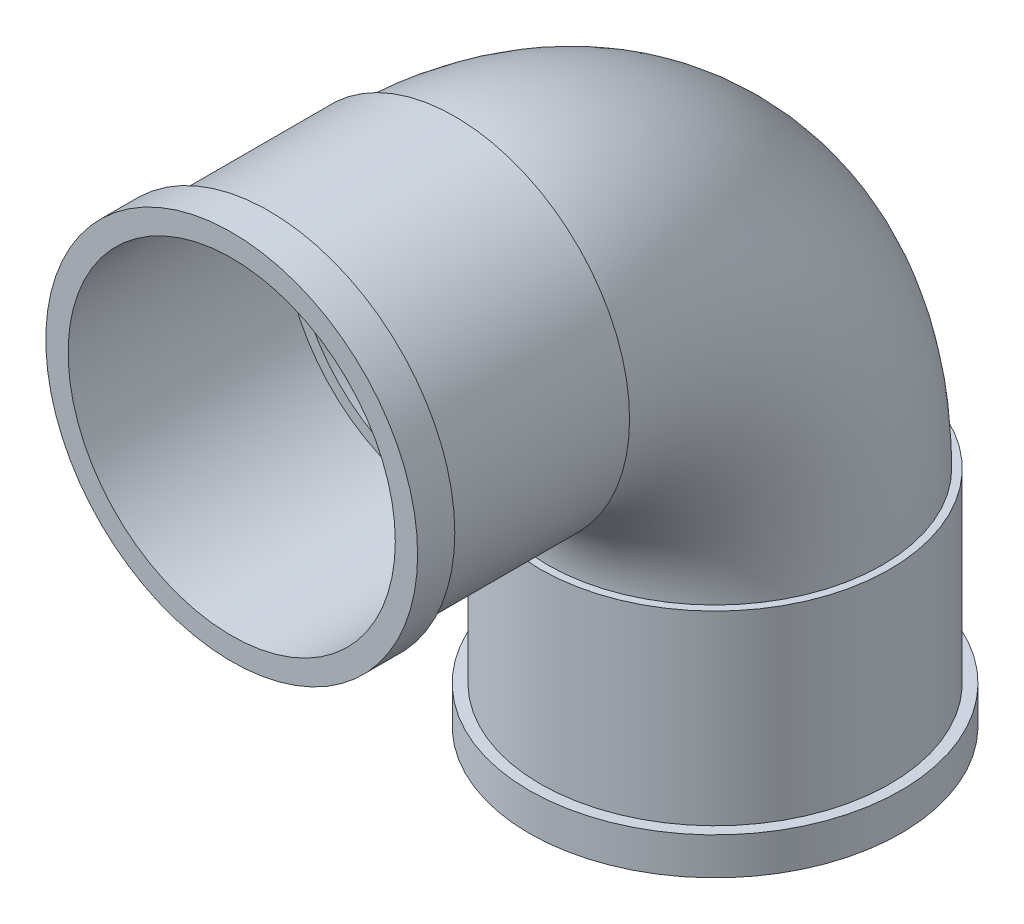
SolidWorks part; units mm, degrees
note: The reader was unsure of these and kept them because the rebuilt part matched: shared geometry of "Skeleton<3>", "Sketch6<5>", "Sketch4<2>", "Sketch36<3>".
ref_plane "Front Plane" through (0, 0, 0) normal (0, 0, 1) x (1, 0, 0)
ref_plane "Top Plane" through (0, 0, 0) normal (0, 1, 0) x (1, 0, 0)
ref_plane "Right Plane" through (0, 0, 0) normal (1, 0, 0) x (0, 0, -1)
sketch "Skeleton" plane through (0, 0, 0) normal (0, 0, 1) x (1, 0, 0)
  circle A0 centre (0, 0) radius 20.5
  circle A1 centre (0, 0) radius 23.5
  circle A2 centre (0, 0) radius 22
  dimension "D1" = 41
  dimension "D2" = 47
  dimension "D3" = 44
extrude "Boss-Extrude1" add sketch "Skeleton" against normal blind 30 contours A1 A2 | A2 A0
extrude "Cut-Extrude1" cut sketch "Skeleton<3>" against normal blind 29 contours A2 A0
sketch "Skeleton<3>" plane through (0, 0, 0) normal (0, 0, 1) x (1, 0, 0) same geometry as "Skeleton"
sketch "Sketch4" plane through (0, 0, 0) normal (1, 0, 0) x (0, 0, -1)
  line L0 (0, 0) -> (65, 0) construction
  line L1 (65, 0) -> (65, -65) construction
  line L2 (30, -23.5) -> (30, 23.5) construction
  line L3 (30, 0) -> (29.0749, 0)
  line L4 (65, -35) -> (65, -36.3627)
  arc A0 (30, 0) -> (65, -35) centre (30, -35) cw
  point P3 (65, -35)
  point P6 (30, 0)
  dimension "D1" = 65
  dimension "D2" = 30
  dimension "D3" = 30
sketch "Sketch6" plane through (0, 0, 0) normal (0, 1, 0) x (1, 0, 0)
  line L0 (0, 0) -> (0, 65) construction
  line L1 (0, 0) -> (0, 65)
  circle A0 centre (0, 65) radius 20.5
  circle A1 centre (0, 65) radius 23.5
  circle A2 centre (0, 65) radius 22
extrude "Boss-Extrude3" add sketch "Sketch6" along normal blind 30 from vertex at -65 separate body starting at point (0, -65, -65)
extrude "Cut-Extrude2" cut sketch "Sketch6<5>" along normal blind 29 from surface
sketch "Sketch6<5>" plane through (0, 0, 0) normal (0, 1, 0) x (1, 0, 0) same geometry as "Sketch6"
sweep "Sweep1" add path "Sketch4" circular profile diameter 45 parameters "D3"=45
sweep "Cut-Sweep1" cut path "Sketch4<2>" circular profile diameter 41 parameters "D3"=41
sketch "Sketch4<2>" plane through (0, 0, 0) normal (1, 0, 0) x (0, 0, -1) same geometry as "Sketch4"
sketch "Sketch36" plane through (0, 0, 0) normal (1, 0, 0) x (0, 0, -1)
  line L1 (0, 23.5) -> (5, 23.5)
  line L2 (0, 23.5) -> (0, 25)
  line L3 (0, 25) -> (5, 25)
  line L4 (5, 23.5) -> (5, 25)
  line L13 (88.5, -65) -> (90, -65)
  line L14 (88.5, -65) -> (88.5, -60)
  line L15 (88.5, -60) -> (90, -60)
  line L16 (90, -65) -> (90, -60)
  dimension "D1" = 5
  dimension "D2" = 1.5
  dimension "D3" = 5
  dimension "D4" = 1.5
revolve "Revolve1" add sketch "Sketch36" angle 360 about L0
revolve "Revolve2" add sketch "Sketch36<3>" angle 360 about L1
sketch "Sketch36<3>" plane through (0, 0, 0) normal (1, 0, 0) x (0, 0, -1) same geometry as "Sketch36"
